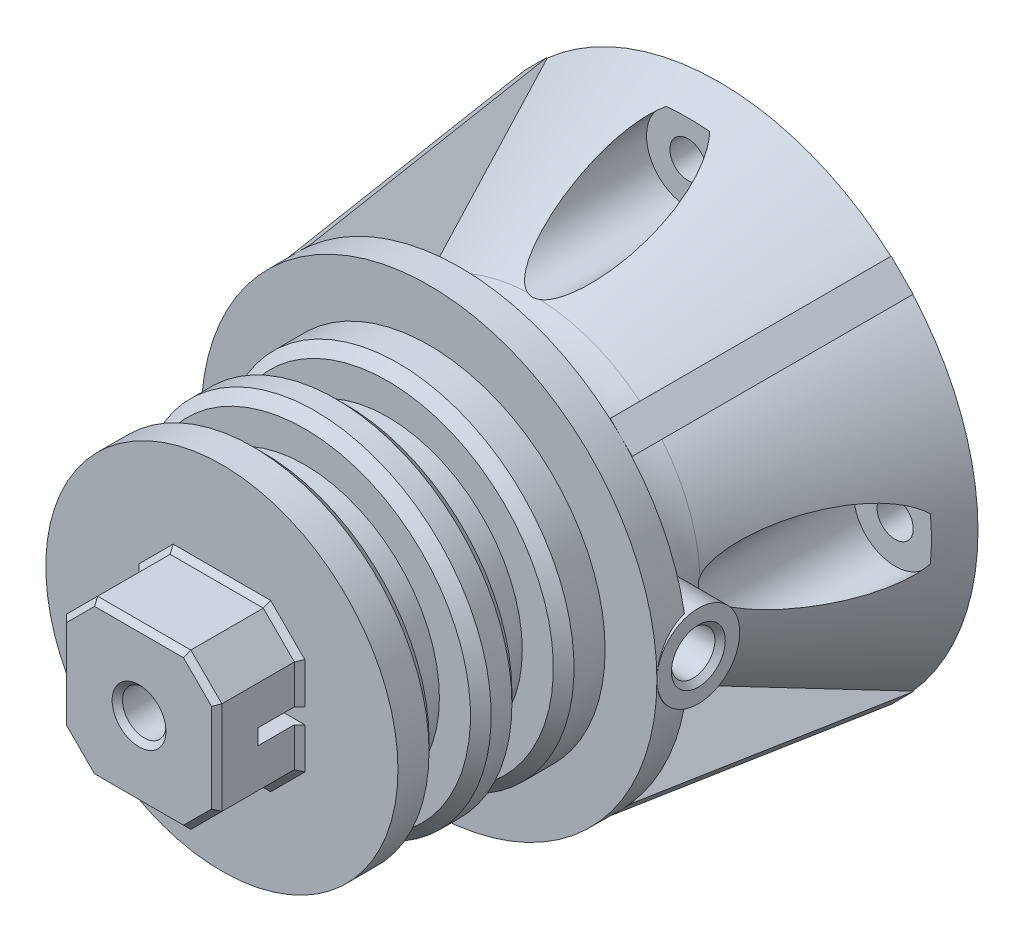
SolidWorks part; units mm, degrees
ref_plane "Front Plane" through (0, 0, 0) normal (0, 0, 1) x (1, 0, 0)
ref_plane "Top Plane" through (0, 0, 0) normal (0, 1, 0) x (1, 0, 0)
ref_plane "Right Plane" through (0, 0, 0) normal (1, 0, 0) x (0, 0, -1)
sketch "Sketch1" plane through (0, 0, 0) normal (0, 0, 1) x (1, 0, 0)
  circle A0 centre (0, 0) radius 25
  dimension "D1" = 50
ref_plane "Plane1" through (0, 0, 20) normal (0, 0, 1) x (1, 0, 0)
sketch "Sketch2" plane through (0, 0, 20) normal (0, 0, 1) x (1, 0, 0)
  circle A0 centre (0, 0) radius 15
  dimension "D1" = 30
loft "Loft1" add profiles "Sketch2", "Sketch1" connector at (-14.1852, 4.8766, 20) connector at (-23.533, 8.4378, 0)
sketch "Sketch3" plane through (0, 0, 20) normal (0, 0, 1) x (1, 0, 0)
  circle A0 centre (0, 0) radius 15
  circle A1 centre (0, 0) radius 15 construction
extrude "Boss-Extrude1" add sketch "Sketch3" along normal blind 5
fillet "Fillet1" radius 10 1 edges at (15, 0, 20)
sketch "Sketch4" plane through (0, 0, 0) normal (0, 0, -1) x (-1, 0, 0)
  line L0 (0, 20) -> (0, -20) construction
  line L1 (-20, 0) -> (20, 0) construction
  circle A0 centre (0, 0) radius 20 construction
  circle A1 centre (0, 20) radius 1.75
  circle A2 centre (-20, 0) radius 1.75
  circle A3 centre (0, -20) radius 1.75
  circle A4 centre (20, 0) radius 1.75
  dimension "D1" = 40
  dimension "D2" = 3.5
  dimension "D3" = 3.5
  dimension "D4" = 3.5
  dimension "D5" = 3.5
extrude "Cut-Extrude1" cut sketch "Sketch4" against normal blind 130
ref_plane "Plane2" through (0, 0, 3) normal (0, 0, -1) x (-1, 0, 0)
sketch "Sketch5" plane through (0, 0, 3) normal (0, 0, -1) x (-1, 0, 0)
  circle A0 centre (0, 20) radius 4
  circle A1 centre (20, 0) radius 4
  circle A3 centre (-20, 0) radius 4
  circle A5 centre (0, -20) radius 4
  dimension "D1" = 8
  dimension "D2" = 8
  dimension "D3" = 8
  dimension "D4" = 8
extrude "Cut-Extrude2" cut sketch "Sketch5" against normal blind 130
sketch "Sketch6" plane through (0, 0, 25) normal (0, 0, 1) x (1, 0, 0)
  circle A0 centre (0, 0) radius 22
  dimension "D1" = 44
extrude "Boss-Extrude2" add sketch "Sketch6" along normal blind 3
sketch "Sketch7" plane through (0, 0, 28) normal (0, 0, 1) x (1, 0, 0)
  circle A0 centre (0, 0) radius 17
  circle A1 centre (0, 0) radius 22 construction
  dimension "D1" = 5
extrude "Boss-Extrude3" add sketch "Sketch7" along normal blind 20
sketch "Sketch8" plane through (0, 0, 0) normal (0, 1, 0) x (1, 0, 0)
  line L0 (0, -48) -> (0, -27)
  line L1 (-17, -48) -> (17, -48) construction
  line L3 (17, -48) -> (17, -28) construction
  line L4 (3, -24) -> (45.4819, -24)
  arc A0 (0, -27) -> (3, -24) centre (3, -27) cw
  point P9 (0, -24)
  dimension "D2" = 3
  dimension "D1" = 24
  dimension "D3" = 17
ref_plane "Plane5" through (14, 0, 0) normal (1, 0, 0) x (0, 0, -1)
sketch "Sketch14" plane through (14, 0, 0) normal (1, 0, 0) x (0, 0, -1)
  line L0 (-28, 22) -> (-28, -22) construction
  circle A0 centre (-24, 0) radius 4
  dimension "D1" = 8
extrude "Boss-Extrude5" add sketch "Sketch14" along normal blind 10
sketch "Sketch9" plane through (0, 0, 48) normal (0, 0, 1) x (1, 0, 0)
  circle A0 centre (0, 0) radius 2.1
  dimension "D1" = 4.2
sweep "Cut-Sweep1" cut profiles "Sketch9" path "Sketch8"
ref_plane "Plane4" through (14, 0, 0) normal (1, 0, 0) x (0, 0, -1)
sketch "Sketch10" plane through (0, 0, 48) normal (0, 0, 1) x (1, 0, 0)
  circle A0 centre (0, 0) radius 10
  circle A1 centre (0, 0) radius 17 construction
  dimension "D1" = 7
extrude "Cut-Extrude3" cut sketch "Sketch10" against normal blind 20
sketch "Sketch11" plane through (0, 0, 28) normal (0, 0, 1) x (1, 0, 0)
  line L0 (7.0711, 7.0711) -> (-7.0711, -7.0711)
  line L1 (0, 0) -> (0, 10)
  circle A0 centre (0, 0) radius 10 construction
  circle A1 centre (0, 0) radius 10 construction
  dimension "D1" = 45
ref_plane "Plane3" through (0, 0, 0) normal (-0.7071, 0.7071, 0) x (-0.7071, -0.7071, 0)
sketch "Sketch12" plane through (0, 0, 0) normal (-0.7071, 0.7071, 0) x (-0.7071, -0.7071, 0)
  line L0 (22, 25) -> (25, 0)
  line L1 (-25, 0) -> (25, 0) construction
  line L4 (14, 25) -> (22, 25)
  line L5 (25, 0) -> (23.882, 0)
  line L6 (24.1056, -0.4472) -> (15.1613, 17.4413)
  line L7 (14, 22.3607) -> (14, 25)
  line L8 (23.882, 0) -> (15.1613, 17.4413)
  line L9 (14, 22.3607) -> (14, 25)
  line L10 (25, 0) -> (16.0557, 17.8885) construction
  arc A2 (14, 22.3607) -> (15.1613, 17.4413) centre (25, 22.3607) ccw
  arc A3 (14, 22.3607) -> (15.1613, 17.4413) centre (25, 22.3607) ccw
  dimension "D1" = 1
extrude "Boss-Extrude4" add sketch "Sketch12" along normal mid plane 3
pattern_circular "CirPattern2" count 4 over 360 about axis through (0, 0, 0) along (0, 0, 1) of "Boss-Extrude4"
sketch "Sketch13" [suppressed] plane through (0, 0, 0) normal (0, 1, 0) x (1, 0, 0)
  line L0 (17, -28) -> (17, -48) construction
  line L1 (-20, -28) -> (20, -28) construction
  line L2 (17, -31.3668) -> (17, -44.6332)
  line L3 (0, -28) -> (0, -48) construction
  line L4 (-17, -28) -> (17, -28) construction
  line L5 (-17, -48) -> (17, -48) construction
  arc A0 (17, -31.3668) -> (17, -44.6332) centre (38.5, -38) ccw
  dimension "D1" = 45
  dimension "D2" = 21.5
  dimension "D3" = 10
ref_plane "Plane14" through (0, 0, 38) normal (0, 0, 1) x (1, 0, 0)
sketch "Sketch15" plane through (0, 0, 0) normal (0, 1, 0) x (1, 0, 0)
  line L0 (-17, -28) -> (-17, -48) construction
  line L1 (-21.4316, -32) -> (-13, -32)
  line L2 (-21.4316, -32) -> (-21.4316, -36)
  line L3 (-21.4316, -36) -> (-13, -36)
  line L4 (-13, -32) -> (-13, -36)
  line L5 (-21.5787, -40) -> (-13, -40)
  line L6 (-21.5787, -40) -> (-21.5787, -44)
  line L7 (-21.5787, -44) -> (-13, -44)
  line L8 (-13, -40) -> (-13, -44)
  line L9 (-17, -28) -> (17, -28) construction
  line L10 (0, -28) -> (0, -48) construction
  line L11 (-17, -48) -> (17, -48) construction
  dimension "D1" = 4
  dimension "D2" = 4
  dimension "D3" = 4
  dimension "D4" = 4
  dimension "D5" = 4
  dimension "D6" = 4
revolve "Cut-Revolve1" cut sketch "Sketch15" angle 360 about L10
sketch "Sketch16" plane through (0, 0, 28) normal (0, 0, 1) x (1, 0, 0)
  circle A0 centre (0, 0) radius 2.5
  circle A1 centre (0, 0) radius 6.5
  dimension "D1" = 4
  dimension "D2" = 5
extrude "Boss-Extrude6" add sketch "Sketch16" along normal blind 10
chamfer "Chamfer1" distance 1 angle 45 5 edges at (17, 0, 36) (-17, 0, 32) (-17, 0, 40) (17, 0, 44) (2.5, 0, 38)
sketch "Sketch17" plane through (24, 0, 0) normal (1, 0, 0) x (0, 0, -1)
  circle A0 centre (-24, 0) radius 4
  dimension "D1" = 8
extrude "Cut-Extrude4" cut sketch "Sketch17" against normal blind 2
chamfer "Chamfer2" distance 0.5 angle 45 1 edges at (22, 0, 21.9)
sketch "Sketch18" plane through (0, 0, 0) normal (0, 0, -1) x (-1, 0, 0)
  circle A0 centre (0, 0) radius 12.5
  dimension "D1" = 25
extrude "Cut-Extrude5" cut sketch "Sketch18" against normal blind 20
sketch "Sketch19" plane through (0, 0, 28) normal (0, 0, 1) x (1, 0, 0)
  circle A0 centre (0, 0) radius 10 construction
  circle A1 centre (0, 0) radius 10
extrude "Boss-Extrude7" add sketch "Sketch19" along normal up to surface (20 mm away) up to face at (10, 0, 48)
sketch "Sketch20" plane through (0, 0, 0) normal (0, 1, 0) x (1, 0, 0)
  line L0 (-17, -48) -> (17, -48) construction
  line L1 (7.5, -48) -> (-7.5, -48)
  line L2 (7.5, -48) -> (7.5, -56)
  line L3 (7.5, -56) -> (-7.5, -56)
  line L4 (-7.5, -48) -> (-7.5, -56)
  line L5 (0, -48) -> (0, -59.2411) construction
  point P6 (5.658, -48)
  point P10 (7.6771, -48)
  dimension "D1" = 15
  dimension "D2" = 7.5
  dimension "D3" = 8
extrude "Boss-Extrude8" add sketch "Sketch20" along normal mid plane 15
sketch "Sketch21" plane through (0, 0, 0) normal (0, 1, 0) x (1, 0, 0)
  line L0 (0, -56) -> (0, -65) construction
  line L1 (-7.5, -56) -> (7.5, -56) construction
  line L2 (-7.5, -48) -> (-7.5, -56) construction
  line L3 (-7.5, -48) -> (-7.5, -52.0096)
  line L4 (7.5, -56) -> (7.5, -48) construction
  line L5 (7.5, -52.0096) -> (7.5, -48)
  line L6 (-7.5, -48) -> (7.5, -48)
  arc A0 (7.5, -52.0096) -> (-7.5, -52.0096) centre (0, -65) ccw
  dimension "D2" = 30
  dimension "D1" = 9
extrude "Cut-Extrude6" cut sketch "Sketch21" against normal mid plane 1.5
sketch "Sketch22" plane through (0, 0, 56) normal (0, 0, 1) x (1, 0, 0)
  circle A0 centre (0, 0) radius 2.1
  dimension "D1" = 4.2
extrude "Cut-Extrude7" cut sketch "Sketch22" against normal blind 28
chamfer "Chamfer3" distance 3 angle 45 4 edges at (7.5, 7.5, 52) (-7.5, 7.5, 52) (-7.5, -7.5, 52) (7.5, -7.5, 52)
chamfer "Chamfer4" distance 0.5 angle 45 19 edges at (6, -6, 56) (0, -7.5, 56) (-6, -6, 56) (-7.5, 0, 56) (-6, 6, 56) (0, 7.5, 56) (6, 6, 56) (7.5, 0, 56) (2.1, 0, 56) (-7.5, 2.625, 48) (-6, 6, 48) (0, 7.5, 48) (6, 6, 48) (7.5, 2.625, 48) (-7.5, -2.625, 48) (7.5, -2.625, 48) (6, -6, 48) (-6, -6, 48) (0, -7.5, 48)
